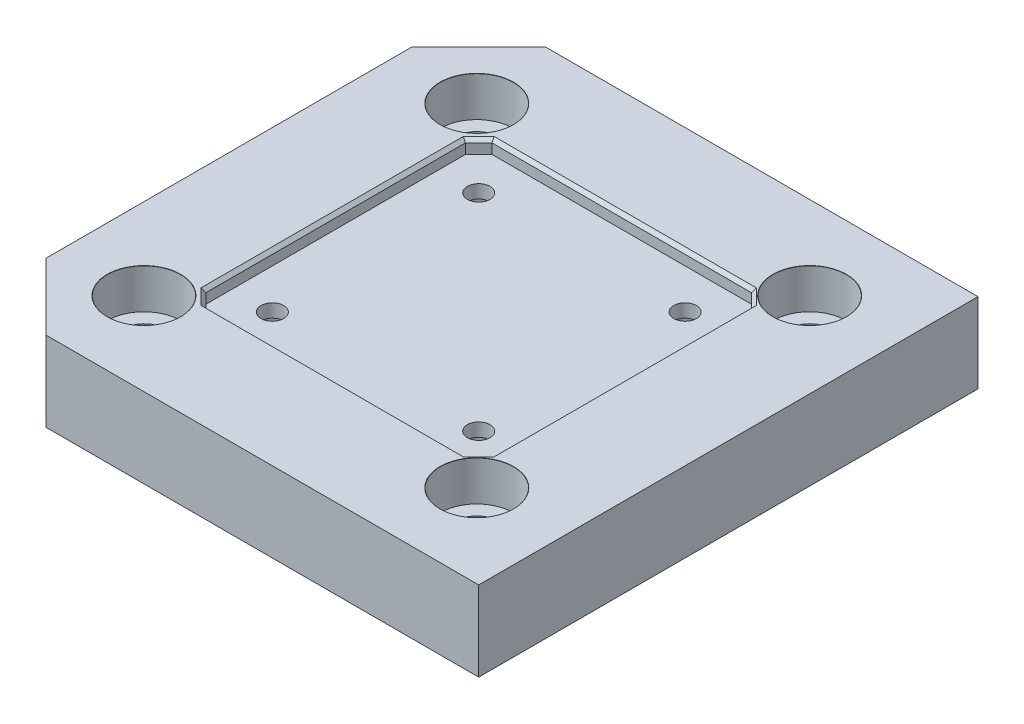
SolidWorks part; units mm, degrees
ref_plane "Front Plane" through (0, 0, 0) normal (0, 0, 1) x (1, 0, 0)
ref_plane "Top Plane" through (0, 0, 0) normal (0, 1, 0) x (1, 0, 0)
ref_plane "Right Plane" through (0, 0, 0) normal (1, 0, 0) x (0, 0, -1)
sketch "Sketch1" plane through (0, 0, 0) normal (0, 1, 0) x (1, 0, 0)
  line L0 (0, 37.5) -> (-37.5, 37.5)
  line L1 (-37.5, 37.5) -> (-37.5, -37.5)
  line L2 (-37.5, -37.5) -> (0, -37.5)
  line L3 (0, -37.5) -> (37.5, -37.5)
  line L4 (37.5, -37.5) -> (37.5, 37.5)
  line L5 (37.5, 37.5) -> (0, 37.5)
  line L6 (-37.5, 37.5) -> (37.5, -37.5) construction
  line L7 (37.5, 37.5) -> (-37.5, -37.5) construction
  point P2 (0, 0)
  dimension "D1" = 75
  dimension "D2" = 37.5
  dimension "D3" = 37.5
extrude "Boss-Extrude1" add sketch "Sketch1" along normal blind 12
sketch "Sketch2" plane through (0, 12, 0) normal (0, -1, 0) x (1, 0, 0)
  line L1 (-25.29, 25) -> (49.71, 25) construction
  line L2 (-25.29, 25) -> (-25.29, -25) construction
  line L3 (-25.29, -25) -> (49.71, -25) construction
  line L4 (49.71, 25) -> (49.71, -25) construction
  line L5 (-25.29, 25) -> (49.71, -25) construction
  line L6 (-25.29, -25) -> (49.71, 25) construction
  point P0 (24.71, -25)
  point P1 (49.71, -25)
  point P2 (12.21, 0)
  point P3 (49.71, 25)
  point P4 (24.71, 25)
  point P9 (0, 0)
  point P10 (-25.29, -25)
  point P11 (-25.29, 25)
  dimension "D1" = 49.71
  dimension "D2" = 25
  dimension "D5" = 25
  dimension "D3" = 75
  dimension "D4" = 50
hole_wizard "CBORE for M6 SHCS1" positions "Sketch13" profile "Sketch14" counterbore size "M6" standard "ANSI Metric" end condition through all
sketch "Sketch13" plane through (0, 12, 0) normal (0, 1, 0) x (1, 0, 0)
  point P15 (-25.29, -25)
  point P18 (-25.29, 25)
  point P21 (24.71, 25)
  point P24 (24.71, -25)
  point P30 (0, 0)
  point P31 (0, 0)
  point P32 (0, 0)
  point P33 (0, 0)
sketch "Sketch14" plane through (-25.29, 12, 25) normal (1, 0, 0) x (0, 0, 1)
  line L0 (0, 0) -> (0, 12)
  line L1 (3.3, 11.975) -> (3.325, 12)
  line L2 (5.5, 6) -> (3.3, 6)
  line L3 (3.3, 6) -> (3.3, 11.975)
  line L5 (5.5, 6) -> (5.5, 0.025)
  line L6 (5.5, 0.025) -> (5.525, 0)
  line L7 (5.525, 0) -> (0, 0)
  line L8 (-5.5, 0.025) -> (-5.525, 0) construction
  line L11 (0, -6.35) -> (0, 107.95) construction
  line L12 (3.325, 12) -> (0, 12)
  line L13 (-3.3, 11.975) -> (-3.325, 12) construction
  dimension "Thru Hole Dia." = 6.6
  dimension "Thru Hole Depth" = 12
  dimension "C'Bore Dia." = 11
  dimension "C'Bore Depth" = 6
  dimension "Near C'Sink Dia." = 11.05
  dimension "Near C'Sink Angle" = 90
  dimension "Far C'Sink Dia." = 6.65
  dimension "Far C'Sink Angle" = 90
sketch "Sketch9" plane through (0, 12, 0) normal (0, 1, 0) x (1, 0, 0)
  line L0 (21.5, 19.5) -> (19.5, 21.5)
  line L1 (-19.5, 21.5) -> (19.5, 21.5)
  line L2 (-21.5, 19.5) -> (-21.5, -19.5)
  line L3 (-19.5, -21.5) -> (19.5, -21.5)
  line L4 (21.5, 19.5) -> (21.5, -19.5)
  line L5 (-20.5, 20.5) -> (20.5, -20.5) construction
  line L6 (-20.5, -20.5) -> (20.5, 20.5) construction
  line L7 (19.5, -21.5) -> (21.5, -19.5)
  line L8 (-21.5, -19.5) -> (-19.5, -21.5)
  line L9 (-19.5, 21.5) -> (-21.5, 19.5)
  point P0 (0, 0)
  point P17 (0, 0)
  dimension "D1" = 4
  dimension "D4" = 2
extrude "Cut-Extrude3" cut sketch "Sketch9" against normal blind 2 contours L2 L8 L3 L7 L4 L0 L1 L9
sketch "Sketch10" plane through (0, 0, 0) normal (0, 1, 0) x (1, 0, 0)
  line L1 (15.5, 15.5) -> (-15.5, 15.5) construction
  line L2 (15.5, 15.5) -> (15.5, -15.5) construction
  line L3 (15.5, -15.5) -> (-15.5, -15.5) construction
  line L4 (-15.5, 15.5) -> (-15.5, -15.5) construction
  line L5 (15.5, 15.5) -> (-15.5, -15.5) construction
  line L6 (15.5, -15.5) -> (-15.5, 15.5) construction
  point P0 (0, 0)
  point P7 (-15.5, -15.5)
  point P8 (-15.5, 15.5)
  point P9 (15.5, 15.5)
  point P10 (15.5, -15.5)
  dimension "D1" = 31
  dimension "D2" = 31
hole_wizard "Hole2" positions "Sketch11" profile "Sketch12" legacy end condition through all
sketch "Sketch11" plane through (0, 0, 0) normal (0, -1, 0) x (-1, 0, 0)
  point P0 (15.5, 15.5)
  point P3 (-15.5, 15.5)
  point P6 (-15.5, -15.5)
  point P9 (15.5, -15.5)
sketch "Sketch12" plane through (-15.5, 0, -15.5) normal (1, 0, 0) x (0, 0, -1)
  line L0 (0, 0) -> (0, 12)
  line L1 (1.7, 11.975) -> (1.725, 12)
  line L2 (3.25, 8) -> (1.7, 8)
  line L3 (1.7, 8) -> (1.7, 11.975)
  line L5 (3.25, 8) -> (3.25, 0.025)
  line L6 (3.25, 0.025) -> (3.275, 0)
  line L7 (3.275, 0) -> (0, 0)
  line L8 (-3.25, 0.025) -> (-3.275, 0) construction
  line L11 (0, -6.35) -> (0, 107.95) construction
  line L12 (1.725, 12) -> (0, 12)
  line L13 (-1.7, 11.975) -> (-1.725, 12) construction
  dimension "Thru Hole Dia." = 3.4
  dimension "Thru Hole Depth" = 12
  dimension "C'Bore Dia." = 6.5
  dimension "C'Bore Depth" = 8
  dimension "Near C'Sink Dia." = 6.55
  dimension "Near C'Sink Angle" = 90
  dimension "Far C'Sink Dia." = 3.45
  dimension "Far C'Sink Angle" = 90
chamfer "Chamfer1" distance 0.5 angle 45 8 edges at (20.5, 12, 20.5) (21.5, 12, 0) (20.5, 12, -20.5) (0, 12, 21.5) (-20.5, 12, 20.5) (-21.5, 12, 0) (-20.5, 12, -20.5) (0, 12, -21.5)
chamfer "Chamfer2" distance 10 angle 45 2 edges at (-37.5, 6, 37.5) (-37.5, 6, -37.5)
